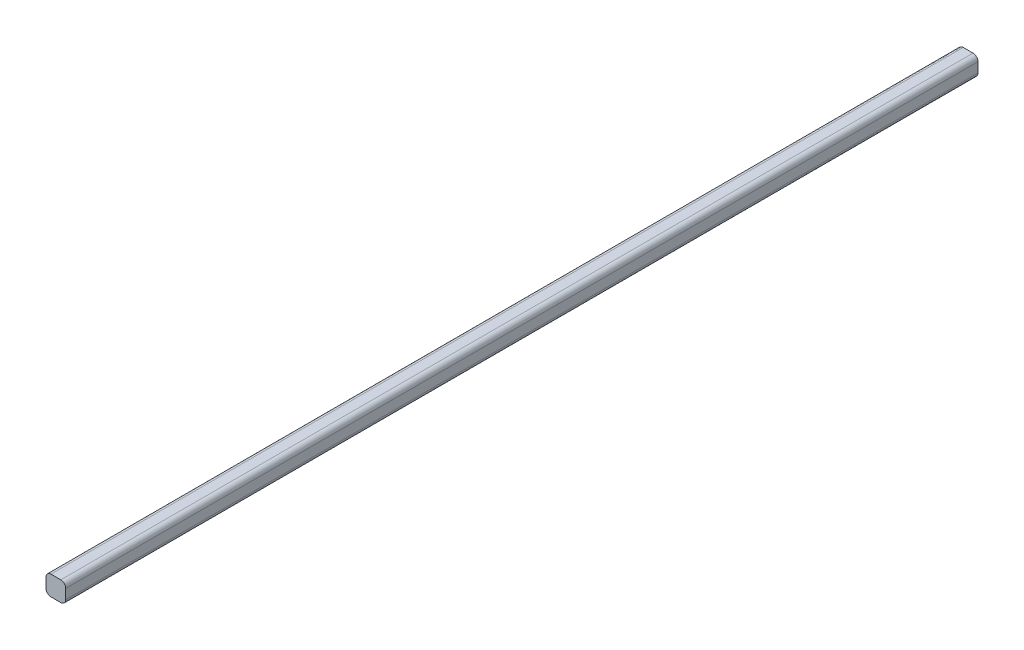
SolidWorks part; units mm, degrees
ref_plane "Plan de face" through (0, 0, 0) normal (0, 0, 1) x (1, 0, 0)
ref_plane "Plan de dessus" through (0, 0, 0) normal (0, 1, 0) x (1, 0, 0)
ref_plane "Plan de droite" through (0, 0, 0) normal (1, 0, 0) x (0, 0, -1)
sketch "Esquisse1" plane through (0, 0, 0) normal (0, 0, 1) x (1, 0, 0)
  line L1 (0, 0) -> (40, 0)
  line L2 (0, 0) -> (0, 40)
  line L3 (0, 40) -> (40, 40)
  line L4 (40, 0) -> (40, 40)
  dimension "D1" = 40
  dimension "D2" = 40
extrude "Boss.-Extru.1" add sketch "Esquisse1" along normal blind 1850
fillet "Congé1" radius 10 4 edges at (0, 0, 925) (40, 0, 925) (0, 40, 925) (40, 40, 925)
